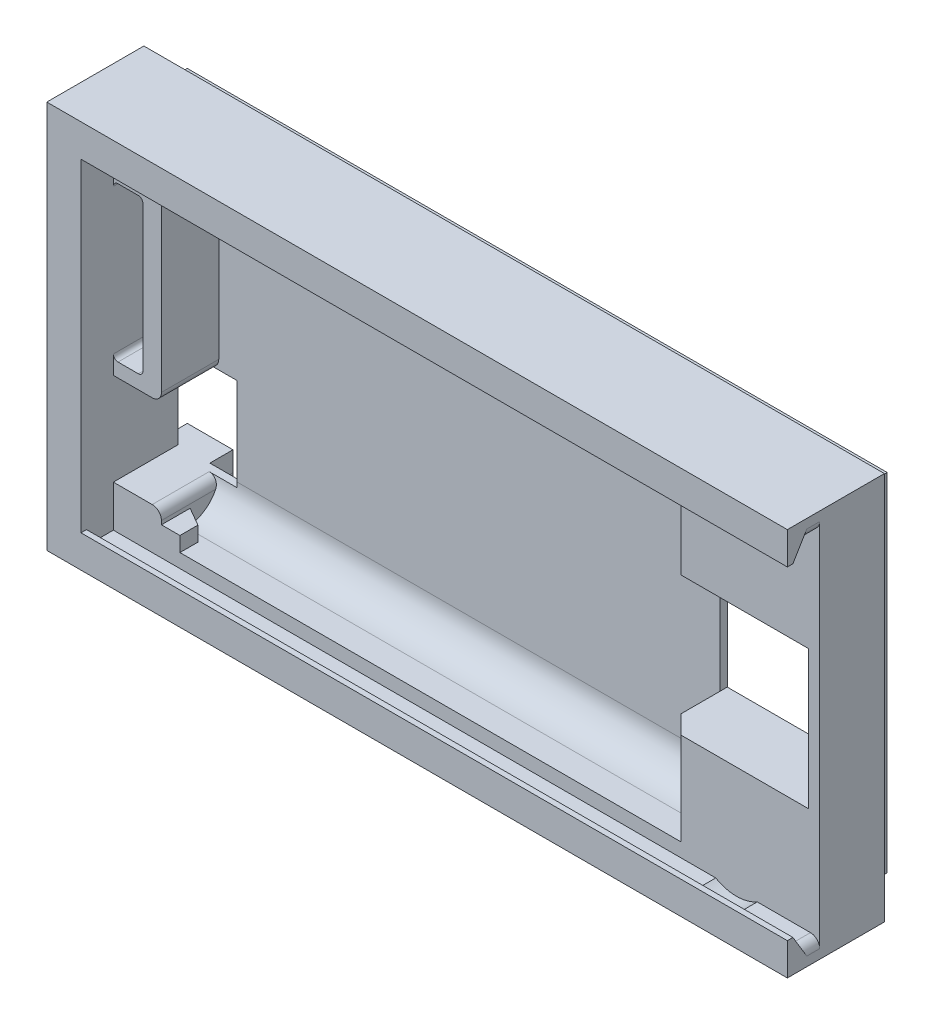
SolidWorks part; units mm, degrees
ref_plane "Front Plane" through (0, 0, 0) normal (0, 0, 1) x (1, 0, 0)
ref_plane "Top Plane" through (0, 0, 0) normal (0, 1, 0) x (1, 0, 0)
ref_plane "Right Plane" through (0, 0, 0) normal (1, 0, 0) x (0, 0, -1)
sketch "Sketch1" plane through (0, 0, 0) normal (0, 0, 1) x (1, 0, 0)
  line L1 (-26.5, 17) -> (26.5, 17)
  line L2 (-26.5, 17) -> (-26.5, -17)
  line L3 (-26.5, -17) -> (26.5, -17)
  line L4 (26.5, 17) -> (26.5, -17)
  line L5 (-26.5, 17) -> (26.5, -17) construction
  line L6 (-26.5, -17) -> (26.5, 17) construction
  point P0 (0, 0)
  dimension "D1" = 34
  dimension "D2" = 53
sketch "Sketch2" plane through (0, 0, 0) normal (0, 0, 1) x (1, 0, 0)
  line L1 (-32.3, 19) -> (44.1, 19)
  line L2 (-32.3, 19) -> (-32.3, -19)
  line L3 (-32.3, -19) -> (44.1, -19)
  line L4 (44.1, 19) -> (44.1, -19)
  line L6 (-26.5, 17) -> (-26.5, -17) construction
  line L7 (26.5, 17) -> (26.5, -17) construction
  line L8 (-26.5, -17) -> (-26.5, -19) construction
  line L9 (-26.5, 17) -> (-26.5, 19) construction
  line L10 (-26.5, 17) -> (26.5, 17) construction
  dimension "D1" = 5.8
  dimension "D2" = 17.6
  dimension "D3" = 2
extrude "Boss-Extrude1" add sketch "Sketch2" along normal blind 7
sketch "Sketch3" plane through (0, 0, 0) normal (1, 0, 0) x (0, 0, -1)
  line L0 (-7.3, 17) -> (-4.3, 17) construction
  line L1 (-1.3, 0) -> (-7.3, 0) construction
  line L2 (-7.3, -17) -> (-7.3, 17) construction
  line L3 (-1.3, -14) -> (-1.3, 14) construction
  line L4 (-7.3, -17) -> (-4.3, -17) construction
  line L5 (-7.8, 17.5) -> (-4.3, 17.5)
  line L6 (-0.8, -14) -> (-0.8, 14)
  line L7 (-7.8, -17.5) -> (-4.3, -17.5)
  line L8 (-7.8, -17.5) -> (-7.8, 17.5)
  arc A0 (-4.3, 17) -> (-1.3, 14) centre (-4.3, 14) cw construction
  arc A1 (-4.3, -17) -> (-1.3, -14) centre (-4.3, -14) ccw construction
  arc A2 (-4.3, 17.5) -> (-0.8, 14) centre (-4.3, 14) cw
  arc A3 (-4.3, -17.5) -> (-0.8, -14) centre (-4.3, -14) ccw
  point P6 (-12.641, 14.088)
  point P11 (-13.7836, 13.0913)
  dimension "D1" = 3
  dimension "D2" = 6
  dimension "D3" = 34
  dimension "D5" = 0.8
  dimension "D4" = 0.5
extrude "Cut-Battery" cut sketch "Sketch3" against normal mid plane 54.2
sketch "Sketch4" plane through (0, 0, 7) normal (0, 0, 1) x (1, 0, 0)
  line L1 (0, 0) -> (34, 0) construction
  line L2 (40.9, 7.5) -> (27.1, 7.5)
  line L3 (40.9, 7.5) -> (40.9, -7.5)
  line L4 (40.9, -7.5) -> (27.1, -7.5)
  line L7 (27.1, 7.5) -> (27.1, -7.5)
  line L8 (40.9, 7.5) -> (27.1, -7.5) construction
  line L9 (40.9, -7.5) -> (27.1, 7.5) construction
  line L10 (27.1, -14) -> (27.1, 14) construction
  line L12 (27.1, 17.5) -> (27.1, -17.5) construction
  line L13 (44.1, -19) -> (44.1, 19) construction
  point P0 (34, 0)
  point P9 (31.3029, -7.5)
  point P12 (27.1, -5.5675)
  dimension "D1" = 15
  dimension "D2" = 3.2
extrude "ForFinger" cut sketch "Sketch4" against normal through all
sketch "Sketch5" plane through (0, 17.5, 0) normal (0, -1, 0) x (1, 0, 0)
  line L0 (-27.1, 7) -> (-25.1, 7)
  line L1 (27.1, 7) -> (-27.1, 7) construction
  line L2 (-25.1, 7) -> (-25.1, 3.9)
  line L3 (-25.1, 3.9) -> (-27.1, 3.9)
  line L4 (-27.1, 3.9) -> (-27.1, 7)
  line L5 (-26.9, 3.8) -> (-24.9, 3.8) construction
  line L6 (-24.9, 3.8) -> (-24.9, 6.8) construction
  line L7 (-24.9, 6.8) -> (-20.5432, 6.8) construction
  line L8 (-26.9, 3.8) -> (-26.9, 0.8) construction
  line L9 (-26.9, 0.8) -> (-20.5432, 0.8) construction
  line L10 (-20.5432, 0.8) -> (-20.5432, 6.8) construction
  line L11 (-27.1, 0.8) -> (27.1, 0.8) construction
  line L12 (-27.1, 0.8) -> (-27.1, 4.3) construction
  point P9 (0, 0)
  point P14 (0, 0)
  point P15 (-20.5432, 1)
  point P18 (-24.4325, 2.1847)
  point P19 (-24.0137, 1)
  point P20 (-26.3689, 1)
  point P23 (-27.1, 3.7068)
  point P24 (-25.203, 5.2626)
  point P25 (-27.1, 4.2847)
  point P26 (-25.0697, 4.2847)
  dimension "D1" = 6
  dimension "D2" = 3
  dimension "D3" = 0.2
  dimension "D4" = 2
  dimension "D5" = 0.2
  dimension "D6" = 0.1
extrude "Boss-Extrude2" add sketch "Sketch5" along normal blind 1.6
chamfer "Chamfer1" distance 2 angle 30 1 edges at (-25.1, 16.6885, 3.9) first distance on face at (-26.1, 16.6885, 3.9)
mirror "Mirror1" about plane through (0, 0, 0) normal (0, 1, 0) of "Chamfer1", "Boss-Extrude2"
sketch "Sketch6" plane through (0, 0, 7) normal (0, 0, 1) x (1, 0, 0)
  line L1 (-32.3, -4.5) -> (-25.1, -4.5)
  line L2 (-32.3, -4.5) -> (-32.3, -14.5)
  line L3 (-32.3, -14.5) -> (-25.1, -14.5)
  line L4 (-25.1, -4.5) -> (-25.1, -14.5)
  line L7 (-26.5, -17) -> (26.5, -17) construction
  line L8 (-32.3, 19) -> (-32.3, -19) construction
  point P4 (-30.9225, -14.5)
  point P6 (-24.7465, -4.5)
  point P8 (-32.3, -9.5)
  dimension "D1" = 10
  dimension "D2" = 7.5
  dimension "D3" = 7.2
extrude "Cut-Connector" cut sketch "Sketch6" against normal through all
sketch "Sketch9" plane through (0, 0, 0) normal (0, 0, 1) x (1, 0, 0)
  line L0 (44.1, -19) -> (-32.3, -19)
  line L1 (-32.3, -19) -> (-32.3, 19)
  line L2 (-32.3, 19) -> (44.1, 19)
  line L3 (44.1, 19) -> (44.1, 21)
  line L4 (44.1, 21) -> (-34.3, 21)
  line L5 (-34.3, 21) -> (-34.3, -21)
  line L6 (-34.3, -21) -> (44.1, -21)
  line L7 (44.1, -21) -> (44.1, -19)
  line L8 (44.1, -19) -> (44.1, 19) construction
  point P13 (0, 0)
  point P14 (34.8579, -18)
  dimension "D1" = 2
  dimension "D2" = 2
extrude "Boss-Extrude3" add sketch "Sketch9" along normal offset from surface (10.5 mm away) 3.5 up to face at (-2.98, -1.9, 7) offset beyond the face yes
sketch "Sketch10" plane through (0, 0, 7) normal (0, 0, 1) x (1, 0, 0)
  line L0 (44.1, 19) -> (44.1, 21) construction
  line L1 (13.6743, 19.6) -> (35.1, 19.6) construction
  line L3 (-32.3, 19) -> (44.1, 19) construction
  line L4 (0, 0) -> (44.1, 0) construction
  line L5 (44.1, -19) -> (44.1, 19) construction
  circle A0 centre (35.1, 15.1) radius 4.5
  circle A1 centre (35.1, -15.1) radius 4.5
  dimension "D1" = 9
  dimension "D2" = 9
  dimension "D3" = 0.6
  dimension "D4" = 15.1
extrude "Cut-Latch" cut sketch "Sketch10" along normal blind 2
sketch "Sketch11" plane through (44.1, 0, 0) normal (1, 0, 0) x (0, 0, -1)
  line L0 (-10.5, 19) -> (-9, 19)
  line L1 (-10.5, 19) -> (-7, 19) construction
  line L2 (-9, 19) -> (-9.9, 17.5)
  line L3 (-9.9, 17.5) -> (-10.5, 17.5)
  line L4 (-10.5, -19) -> (-10.5, 19) construction
  line L5 (-10.5, 17.5) -> (-10.5, 19)
  line L8 (0, 0) -> (-12.817, 0) construction
  line L9 (-9.9, -17.5) -> (-10.5, -17.5)
  line L10 (-9, -19) -> (-9.9, -17.5)
  line L11 (-10.5, -19) -> (-9, -19)
  line L12 (-10.5, -17.5) -> (-10.5, -19)
  line L13 (-4.3, 17.5) -> (-7, 17.5) construction
  dimension "D1" = 0.6
  dimension "D2" = 38
  dimension "D3" = 59.036
  dimension "D4" = 1.5
extrude "Boss-Extrude4" add sketch "Sketch11" against normal up to surface (76.4 mm away) up to face at (-32.3, -4.75, 6.125)
fillet "Fillet3" radius 1 2 edges at (44.1, -19, 8) (44.1, 19, 8)
chamfer "Chamfer2" distance 2 angle 45 2 edges at (27.1, -12.5, 7) (27.1, 12.5, 7)
fillet "Fillet2" radius 1 2 edges at (-27.1, -14.5, 3.9179) (-27.1, -4.5, 3.9)
sketch "Sketch12" plane through (0, 0, 7) normal (0, 0, 1) x (1, 0, 0)
  line L0 (-28.1, -4.5) -> (-32.3, -4.5) construction
  line L1 (-32.3, 13.7) -> (-29.1, 13.7)
  line L2 (-32.3, 13.7) -> (-32.3, -3)
  line L3 (-32.3, -3) -> (-29.1, -3)
  line L4 (-29.1, 13.7) -> (-29.1, -3)
  line L5 (-27.1, -3.5) -> (-27.1, 14) construction
  line L6 (-32.3, 19) -> (-32.3, -4.5) construction
  point P9 (-31.7, 13.1487)
  dimension "D1" = 1.5
  dimension "D2" = 2
  dimension "D3" = 3.2
  dimension "D4" = 16.7
extrude "Cut-Extrude6" cut sketch "Sketch12" against normal through all
fillet "Fillet1" radius 0.5 4 edges at (-29.1, 13.7, 3.5) (-32.3, 13.7, 3.5) (-32.3, -3, 3.5) (-29.1, -3, 3.5)
sketch "Sketch13" plane through (0, 0, 0) normal (0, 0, -1) x (-1, 0, 0)
  line L0 (33.8, 18.75) -> (33.8, -18.75) construction
  line L1 (34.3, 21) -> (36, 21)
  line L2 (34.3, 21) -> (34.3, -21)
  line L3 (34.3, -21) -> (36, -21)
  line L4 (36, 21) -> (36, -21)
  point P5 (34.3, -21)
  point P9 (34.3, -21)
  point P11 (0, 0)
  point P12 (34.3, 22.474)
  point P13 (36, -22.5129)
  point P14 (0, 0)
  point P15 (34.3, 21)
  point P17 (34.3, -21)
  dimension "D1" = 2.2
extrude "Boss-Extrude5" add sketch "Sketch13" against normal up to surface (10.5 mm away) up to face at (5.4, 0, 10.5)
sketch "Sketch16" plane through (0, 0, 0) normal (0, 0, -1) x (-1, 0, 0)
  circle A0 centre (-39.55, 16.4) radius 1.1
  circle A1 centre (31.45, 16.4) radius 1.1
  circle A2 centre (31.45, -16.4) radius 1.1
  circle A3 centre (-39.55, -16.4) radius 1.1
  circle A4 centre (-39.55, 16.4) radius 1.35 construction
  circle A5 centre (31.45, 16.4) radius 1.35 construction
  circle A6 centre (31.45, -16.4) radius 1.35 construction
  circle A7 centre (-39.55, -16.4) radius 1.35 construction
  dimension "D1" = 2.2
extrude "Cut-Extrude7" cut sketch "Sketch16" against normal offset from surface (3 mm away) 4 up to face at (-3.4992, -0.3944, 7)
sketch "Sketch18" plane through (0, 0, 0) normal (0, 0, -1) x (-1, 0, 0)
  line L0 (-35.9671, 17.75) -> (27.8671, 17.75)
  line L1 (-41.9, 18.75) -> (33.8, 18.75)
  line L2 (-41.9, 18.75) -> (-41.9, -18.75)
  line L3 (-41.9, -18.75) -> (33.8, -18.75)
  line L4 (33.8, 18.75) -> (33.8, -18.75)
  line L5 (-40.9, 12.8171) -> (-40.9, -12.8171)
  line L6 (-41.9, 14.178) -> (-40.9, 14.178) construction
  line L7 (-37.328, 17.75) -> (-37.328, 18.75) construction
  line L8 (-41.9, 0) -> (33.8, 0) construction
  line L9 (-4.05, 18.75) -> (-4.05, -18.75) construction
  line L10 (-35.9671, -17.75) -> (27.8671, -17.75)
  line L11 (32.8, 12.8171) -> (32.8, -12.8171)
  line L12 (28.8623, -16.6528) -> (28.8623, -14.5)
  line L13 (32.3, -14.5) -> (25.1, -14.5) construction
  line L14 (28.8623, -14.5) -> (32.8, -14.5)
  line L15 (32.8, -14.5) -> (32.8, -12.8171)
  arc A0 (-36.9623, 16.6528) -> (-39.8028, 13.8123) centre (-39.55, 16.4) cw
  arc A1 (-36.9623, 16.6528) -> (-35.9671, 17.75) centre (-35.9671, 16.75) cw
  arc A2 (-39.8028, 13.8123) -> (-40.9, 12.8171) centre (-39.9, 12.8171) ccw
  circle A3 centre (-39.55, 16.4) radius 1.1
  circle A4 centre (-39.55, 16.4) radius 1.1 construction
  circle A5 centre (-39.55, -16.4) radius 1.1
  arc A6 (-39.8028, -13.8123) -> (-40.9, -12.8171) centre (-39.9, -12.8171) cw
  arc A7 (-36.9623, -16.6528) -> (-35.9671, -17.75) centre (-35.9671, -16.75) ccw
  arc A8 (-36.9623, -16.6528) -> (-39.8028, -13.8123) centre (-39.55, -16.4) ccw
  arc A10 (28.8623, -16.6528) -> (27.8671, -17.75) centre (27.8671, -16.75) cw
  circle A12 centre (31.45, -16.4) radius 1.1
  circle A13 centre (31.45, 16.4) radius 1.1
  arc A14 (31.7028, 13.8123) -> (32.8, 12.8171) centre (31.8, 12.8171) cw
  arc A15 (28.8623, 16.6528) -> (27.8671, 17.75) centre (27.8671, 16.75) ccw
  arc A16 (28.8623, 16.6528) -> (31.7028, 13.8123) centre (31.45, 16.4) ccw
  point P36 (-40.9, 0)
  point P38 (-4.05, 17.75)
  point P39 (-4.05, -17.75)
  point P53 (32.8, 0)
  point P56 (0, 0)
  dimension "D2" = 2.6
  dimension "D3" = 1
  dimension "D1" = 1
extrude "Boss-Extrude7" add sketch "Sketch18" along normal blind 2.5
chamfer "Chamfer3" distance 2 distance2 7 1 edges at (40.9, 0, 7) first distance on face at (-3.4992, -0.3944, 7)
sketch "Sketch19" plane through (0, 0, -2.5) normal (0, 0, -1) x (-1, 0, 0)
  line L0 (33.8, -18.75) -> (33.8, 18.75) construction
  line L1 (32.8, -14.5) -> (33.8, -14.5)
  line L2 (32.8, -14.5) -> (32.8, -4.5)
  line L3 (32.8, -4.5) -> (33.8, -4.5)
  line L4 (33.8, -14.5) -> (33.8, -4.5)
  line L5 (25.1, -4.5) -> (32.3, -4.5) construction
extrude "Cut-Extrude8" cut sketch "Sketch19" against normal up to surface (2.5 mm away) up to face at (-30.7, 5.35, 0)
hole_wizard "Ø2.0mm Dowel Hole1" positions "Sketch20" profile "Sketch21" hole size "Ø2.0" standard "DIN"
sketch "Sketch20" plane through (0, 0, -2.5) normal (0, 0, -1) x (-1, 0, 0)
  point P0 (-39.55, -16.4)
  point P3 (-39.55, 16.4)
  point P6 (31.45, 16.4)
  point P9 (31.45, -16.4)
sketch "Sketch21" plane through (39.55, -16.4, -2.5) normal (1, 0, 0) x (0, 1, 0)
  line L0 (0, 0) -> (0, 9.4053)
  line L1 (0, 9.4053) -> (1.1, 7.5)
  line L2 (1.1, 7.5) -> (1.1, 0)
  line L5 (1.1, 0) -> (0, 0)
  line L10 (0, 9.4053) -> (-1.1, 7.5) construction
  line L11 (0, -6.35) -> (0, 107.95) construction
  dimension "Hole Dia." = 2.2
  dimension "Hole Depth" = 7.5
  dimension "Drill Angle" = 60
equation "\"D1@Cut-Battery\" = 53 / 2 + 0.6"
equation "\"D2@Cut-Battery\" = 53 / 2 + 0.6"
